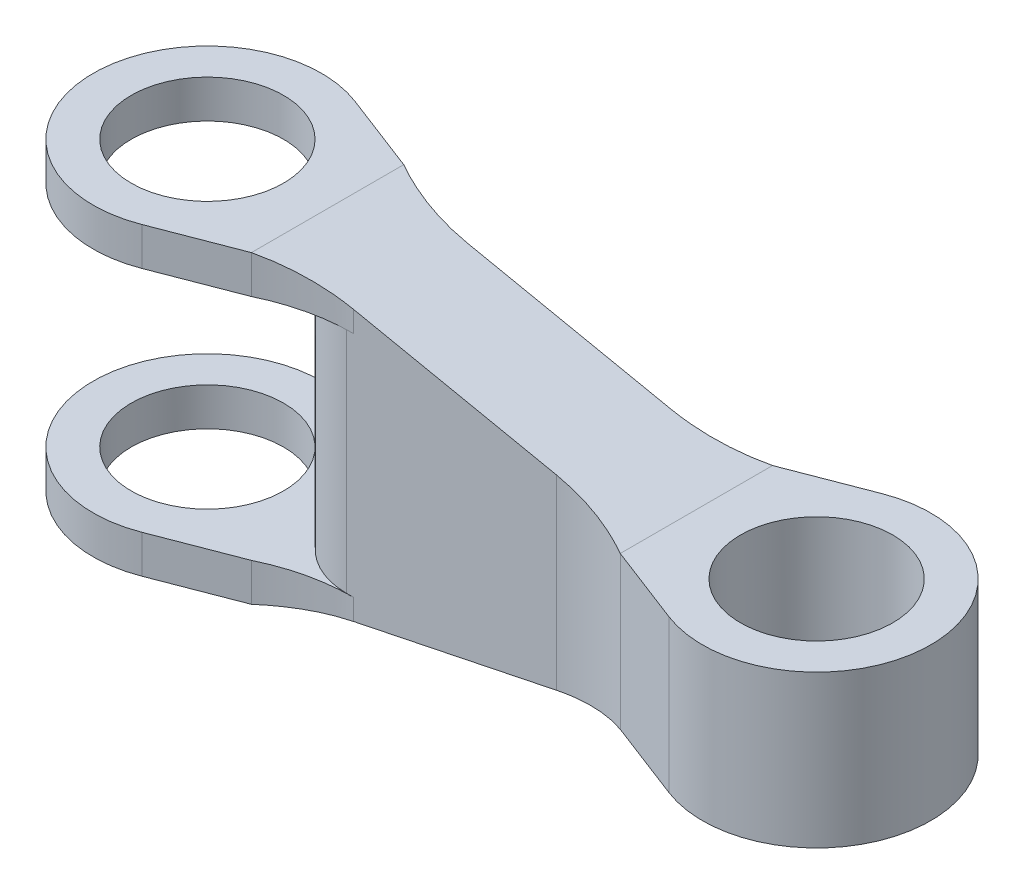
SolidWorks part; units mm, degrees
ref_plane "Front Plane" through (0, 0, 0) normal (0, 0, 1) x (1, 0, 0)
ref_plane "Top Plane" through (0, 0, 0) normal (0, 1, 0) x (1, 0, 0)
ref_plane "Right Plane" through (0, 0, 0) normal (1, 0, 0) x (0, 0, -1)
sketch "Sketch1" plane through (0, 0, 0) normal (0, 1, 0) x (1, 0, 0)
  line L0 (0, 0) -> (40.64, 0) construction
  line L1 (20.32, -22.8401) -> (20.32, 22.8401) construction
  line L2 (2.7357, 7.112) -> (8.0183, 5.08)
  line L3 (8.0183, 5.08) -> (8.0183, 3.81)
  line L4 (8.0183, 3.81) -> (32.6217, 3.81)
  line L5 (32.6217, 3.81) -> (32.6217, 5.08)
  line L6 (32.6217, 5.08) -> (37.9043, 7.112)
  line L7 (32.6217, -5.08) -> (37.9043, -7.112)
  line L8 (32.6217, -3.81) -> (32.6217, -5.08)
  line L9 (8.0183, -3.81) -> (32.6217, -3.81)
  line L10 (8.0183, -5.08) -> (8.0183, -3.81)
  line L11 (2.7357, -7.112) -> (8.0183, -5.08)
  circle A0 centre (0, 0) radius 5.08
  circle A1 centre (40.64, 0) radius 5.08
  arc A2 (2.7357, 7.112) -> (2.7357, -7.112) centre (0, 0) ccw
  arc A3 (37.9043, 7.112) -> (37.9043, -7.112) centre (40.64, 0) cw
  point P16 (20.32, 0)
  dimension "D1" = 10.16
  dimension "D3" = 2.54
  dimension "D4" = 2.54
  dimension "D2" = 40.64
  dimension "D5" = 3.81
  dimension "D6" = 1.27
  dimension "D7" = 2.032
extrude "Boss-Extrude1" add sketch "Sketch1" along normal mid plane 20.32
ref_plane "Plane1" through (0, 0, 13.97) normal (0, 0, 1) x (1, 0, 0)
sketch "Sketch2" plane through (0, 0, 13.97) normal (0, 0, 1) x (1, 0, 0)
  line L0 (-7.62, 10.16) -> (8.0183, 10.16) construction
  line L1 (8.0183, 10.16) -> (32.6217, 10.16) construction
  line L2 (8.0183, 10.16) -> (32.6217, 5.08)
  line L3 (32.6217, 5.08) -> (48.26, 5.08)
  line L4 (48.26, -10.16) -> (48.26, 10.16) construction
  line L5 (0, 0) -> (40.6246, 0) construction
  line L6 (-7.62, 10.16) -> (-7.62, -10.16) construction
  line L7 (-7.62, 7.62) -> (8.0183, 7.62)
  line L8 (-7.62, 7.62) -> (-7.62, -7.62)
  line L9 (-7.62, -7.62) -> (8.0183, -7.62)
  line L10 (8.0183, 7.62) -> (8.0183, -7.62)
  line L11 (8.0183, 10.16) -> (8.0183, -10.16) construction
  line L12 (8.0183, 10.16) -> (48.26, 10.16)
  line L13 (48.26, 10.16) -> (48.26, 5.08)
  line L14 (48.26, -10.16) -> (48.26, -5.08)
  line L15 (-7.62, -10.16) -> (8.0183, -10.16) construction
  line L16 (8.0183, -10.16) -> (48.26, -10.16)
  line L17 (32.6217, -5.08) -> (48.26, -5.08)
  line L18 (8.0183, -10.16) -> (32.6217, -5.08)
  point P22 (-7.62, 0)
  dimension "D1" = 5.08
  dimension "D2" = 2.54
extrude "Cut-Extrude1" cut sketch "Sketch2" against normal through all
fillet "Fillet1" radius 12.7 6 edges at (32.6217, 0, 3.81) (32.6217, 0, -3.81) (8.0183, -8.89, -3.81) (8.0183, 8.89, -3.81) (8.0183, -8.89, 3.81) (8.0183, 8.89, 3.81)
fillet "Fillet2" radius 5.08 2 edges at (8.0183, 0, -3.81) (8.0183, 0, 3.81)
